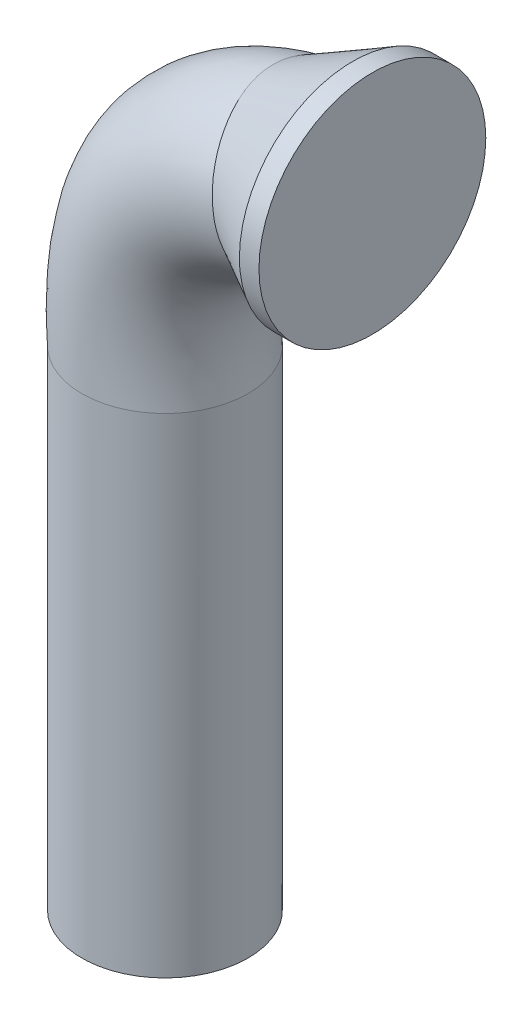
SolidWorks part; units mm, degrees
ref_plane "Alzado" through (0, 0, 0) normal (0, 0, 1) x (1, 0, 0)
ref_plane "Planta" through (0, 0, 0) normal (0, 1, 0) x (1, 0, 0)
ref_plane "Vista lateral" through (0, 0, 0) normal (1, 0, 0) x (0, 0, -1)
sketch "Croquis3" plane through (0, 0, 0) normal (0, 0, 1) x (1, 0, 0)
  spline S0 degree 2 poles (0, 0) (-9.1505, 110.9381) (100, 116) knots 0 0 0 1 1 1
  point P2 (22.2542, 86.5132)
  point P4 (0, 0)
  point P5 (0, 0)
  point P7 (0, 0)
  dimension "D1" = 116
  dimension "D2" = 100
sketch "Croquis4" plane through (0, 0, 0) normal (0, 1, 0) x (1, 0, 0)
  circle A0 centre (0, 0) radius 42.5
  dimension "D1" = 85
sketch "Croquis25" plane through (0, 0, 0) normal (1, 0, 0) x (0, 0, -1)
  line L0 (0, 116) -> (0, 0) construction
  circle A0 centre (0, 116.1096) radius 0.5
  point P4 (0, 116.1096)
  point P5 (0, 0)
  dimension "D1" = 1
extrude "Saliente-Extruir2" add sketch "Croquis25" along normal blind 100
sketch "Croquis26" plane through (0, 0, 0) normal (0, 0, 1) x (1, 0, 0)
  line L0 (-1.9866, 118.5805) -> (97.4685, 118.5805)
  line L1 (97.4685, 118.5805) -> (79.5915, 114.7336)
  line L2 (79.5915, 114.7336) -> (-1.9866, 113.8284)
  line L3 (-1.9866, 113.8284) -> (-1.9866, 118.5805)
extrude "Cortar-Extruir1" cut sketch "Croquis26" against normal through all and the other way through all
sketch "Croquis27" plane through (100, 0, 0) normal (1, 0, 0) x (0, 0, -1)
  line L0 (0, 116) -> (0, 0) construction
  circle A0 centre (0, 116) radius 58
  dimension "D1" = 116
sweep "Barrer1" add profiles "Croquis4" path "Croquis3"
sketch "Croquis31" plane through (0, 0, 0) normal (0, 0, 1) x (1, 0, 0)
  line L0 (96.0807, 162.0316) -> (96.0807, 68.5211)
  line L1 (96.0807, 68.5211) -> (107.9866, 68.5211)
  line L2 (107.9866, 68.5211) -> (107.9866, 162.0316)
  line L3 (107.9866, 162.0316) -> (96.0807, 162.0316)
extrude "Cortar-Extruir2" cut sketch "Croquis31" against normal through all and the other way through all
sketch "Croquis32" plane through (96.0807, 0, 0) normal (1, 0, 0) x (0, 0, -1)
  circle A0 centre (0, 116) radius 58
extrude "Saliente-Extruir3" add sketch "Croquis32" along normal blind 10
sketch "Croquis33" plane through (0, 0, 0) normal (0, 0, 1) x (1, 0, 0)
  line L0 (96.0807, 174) -> (55.1985, 152.1336)
  line L1 (55.1985, 152.1336) -> (55.1985, 116)
  line L2 (55.1985, 116) -> (100, 116)
  line L3 (100, 58) -> (100, 174) construction
  line L4 (100, 116) -> (100, 174)
  line L5 (106.0807, 174) -> (96.0807, 174) construction
  line L6 (100, 174) -> (96.0807, 174)
  spline S0 degree 3 poles (96.0807, 158.2375) (95.9953, 158.2329) (95.8092, 158.2228) (95.5225, 158.2069) (94.7216, 158.1616) (93.0858, 158.0621) (90.1258, 157.8542) (86.2956, 157.5278) (81.8149, 157.0596) (77.3015, 156.4913) (73.3988, 155.9123) (70.169, 155.3752) (66.9662, 154.7972) (63.2483, 154.0542) (59.1294, 153.1299) (55.153, 152.1382) (51.2446, 151.064) (47.4474, 149.9186) (43.9692, 148.7739) (41.7262, 147.9795) (40.1309, 147.3946) (38.71, 146.8628) (36.2627, 145.9056) (33.0596, 144.5741) (29.43, 142.9454) (25.7303, 141.1483) (22.1726, 139.2864) (18.7162, 137.3409) (15.9399, 135.6633) (14.124, 134.5084) (12.5027, 133.4538) (10.0002, 131.7674) (6.4275, 129.178) (2.5313, 126.1013) (-1.1937, 122.9034) (-4.6918, 119.6387) (-7.3914, 116.9069) (-10.0666, 114.0395) (-12.7815, 110.9387) (-15.9815, 106.9394) (-19.0552, 102.7359) (-22.0721, 98.2025) (-24.4857, 94.1785) (-25.9667, 91.4955) (-26.6481, 90.2196) (-27.1767, 89.2147) (-28.2462, 87.1229) (-29.631, 84.2428) (-31.2061, 80.6956) (-32.6633, 77.1402) (-34.0827, 73.355) (-35.4349, 69.3888) (-36.5389, 65.7936) (-37.2056, 63.4113) (-37.6269, 61.8429) (-37.9988, 60.4178) (-38.6618, 57.7238) (-39.4246, 54.3096) (-40.2235, 50.2344) (-40.9285, 46.074) (-41.5342, 41.8366) (-42.0421, 37.5267) (-42.3695, 34.0307) (-42.6402, 30.5029) (-42.8588, 26.8989) (-43.0312, 22.386) (-43.1065, 17.6649) (-43.0786, 12.929) (-42.9494, 8.1242) (-42.7741, 4.3763) (-42.6375, 2.0903) (-42.587, 1.299) (-42.5659, 0.975) (-42.5444, 0.6504) (-42.5225, 0.3254) (-42.5075, 0.1085) (-42.5, 0) knots 0 0 0 0 0.001069 0.00233 0.003589 0.011097 0.022819 0.040685 0.059153 0.079138 0.097553 0.108474 0.12007 0.13824 0.15587 0.172841 0.18947 0.20654 0.222422 0.235245 0.236287 0.243664 0.254212 0.269139 0.287027 0.303942 0.320553 0.337222 0.353522 0.361102 0.364125 0.377701 0.398826 0.419276 0.439754 0.46019 0.479081 0.48776 0.509214 0.530592 0.551778 0.574301 0.598653 0.610424 0.612611 0.616737 0.624618 0.641982 0.656683 0.673136 0.690014 0.707217 0.725517 0.737025 0.738143 0.74582 0.755438 0.772826 0.789551 0.807352 0.825576 0.84306 0.861602 0.86947 0.887293 0.906739 0.925927 0.946319 0.965944 0.986014 0.993223 0.994574 0.995927 0.997282 0.99864 1 1 1 1 construction
  point P5 (100, 115.1523)
revolve "Revolución1" add sketch "Croquis33" angle 360 about L2
sketch "Croquis34" plane through (0, 0, 0) normal (0, -1, 0) x (1, 0, 0)
  circle A0 centre (0, 0) radius 42.5
extrude "Saliente-Extruir4" add sketch "Croquis34" along normal blind 250
